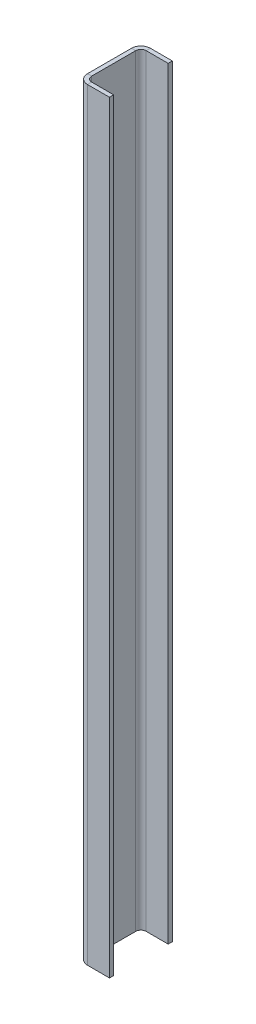
SolidWorks part; units mm, degrees
note: The reader was unsure of these and kept them because the rebuilt part matched: flange length of "Edge-Flange1".
material "AISI 304"
ref_plane "Front" through (0, 0, 0) normal (0, 0, 1) x (1, 0, 0)
ref_plane "Top" through (0, 0, 0) normal (0, 1, 0) x (1, 0, 0)
ref_plane "Right" through (0, 0, 0) normal (1, 0, 0) x (0, 0, -1)
sketch "Sketch1" plane through (0, 0, 0) normal (1, 0, 0) x (0, 0, -1)
  line L1 (-15, -182) -> (15, -182)
  line L2 (-15, -182) -> (-15, 182)
  line L3 (-15, 182) -> (15, 182)
  line L4 (15, -182) -> (15, 182)
  line L5 (-15, -182) -> (15, 182) construction
  line L6 (-15, 182) -> (15, -182) construction
  point P0 (0, 0)
  dimension "D1" = 30
  dimension "D2" = 364
base flange "Base-Flange1" sketch "Sketch1" thickness 2 reverse thickness direction no parameters "D1"=8
edge flange "Edge-Flange1" sketch "Sketch8" flange profiles "Sketch8", "Sketch10" flange angle 90 flange length 15 flange position material inside bend radius 2.5 thickness 2 relief rectangular parameters "D6"=10, "D8"=1
sketch "Sketch8" plane through (0, 0, -15) normal (0, 0, -1) x (0, 1, 0)
  line L2 (-182, 0) -> (-182, 13)
  line L3 (-182, 13) -> (182, 13)
  line L4 (182, 13) -> (182, 0)
  line L7 (-182, 0) -> (182, 0) construction
  line L8 (-182, 0) -> (182, 0)
sketch "Sketch10" plane through (0, 0, 15) normal (0, 0, 1) x (0, -1, 0)
  line L0 (-182, 0) -> (182, 0) construction
  line L1 (-182, 0) -> (182, 0)
  line L2 (-182, 0) -> (-182, 13)
  line L3 (-182, 13) -> (182, 13)
  line L4 (182, 13) -> (182, 0)
bend "EdgeBend1" bend radius 2.5 bend angle 90 parameters "D5"=1
bend "EdgeBend2" bend radius 2.5 bend angle 90 parameters "D5"=3
sketch "Bend-Lines1" [suppressed] plane through (0, 0, 0) normal (0, 1, 0) x (1, 0, 0)
sketch "Bounding-Box1" [suppressed] plane through (0, 0, 0) normal (0, 1, 0) x (1, 0, 0)
sheet metal parameters "Sheet-Metal1" thickness 2 parameters "D1"=8
flat pattern "Flat-Pattern1" [suppressed]
sketch "Bend-Lines2" plane through (0, 0, 0) normal (0, 1, 0) x (1, 0, 0)
sketch3d "Bounding-Box2" [suppressed]
  line L0 (15, 191, 0) -> (15, -191, 0) construction
  line L1 (-15, 191, 0) -> (-15, -191, 0) construction
  line L2 (15, 191, 0) -> (-15, 191, 0) construction
  line L3 (15, -191, 0) -> (-15, -191, 0) construction
sheet metal parameters "Sheet-Metal2" thickness 2 parameters "D1"=8
flat pattern "Flat-Pattern1"
sketch "Bend-Lines2" plane through (0, 0, 0) normal (1, 0, 0) x (0, 0, -1)
  line L0 (13.2489, -182) -> (13.2489, 182) construction
  line L1 (13.2489, -182) -> (13.2489, 182) construction
  line L2 (-13.2489, 182) -> (-13.2489, -182) construction
  line L3 (-13.2489, 182) -> (-13.2489, -182) construction
sketch3d "Bounding-Box2" [suppressed]
  line L0 (-26.4978, 182, 0) -> (-26.4978, -182, 0) construction
  line L1 (26.4978, 182, 0) -> (26.4978, -182, 0) construction
  line L2 (-26.4978, 182, 0) -> (26.4978, 182, 0) construction
  line L3 (-26.4978, -182, 0) -> (26.4978, -182, 0) construction
bend of the flat pattern "Flatten-<EdgeBend1>1"
bend of the flat pattern "Flatten-<EdgeBend2>1"
